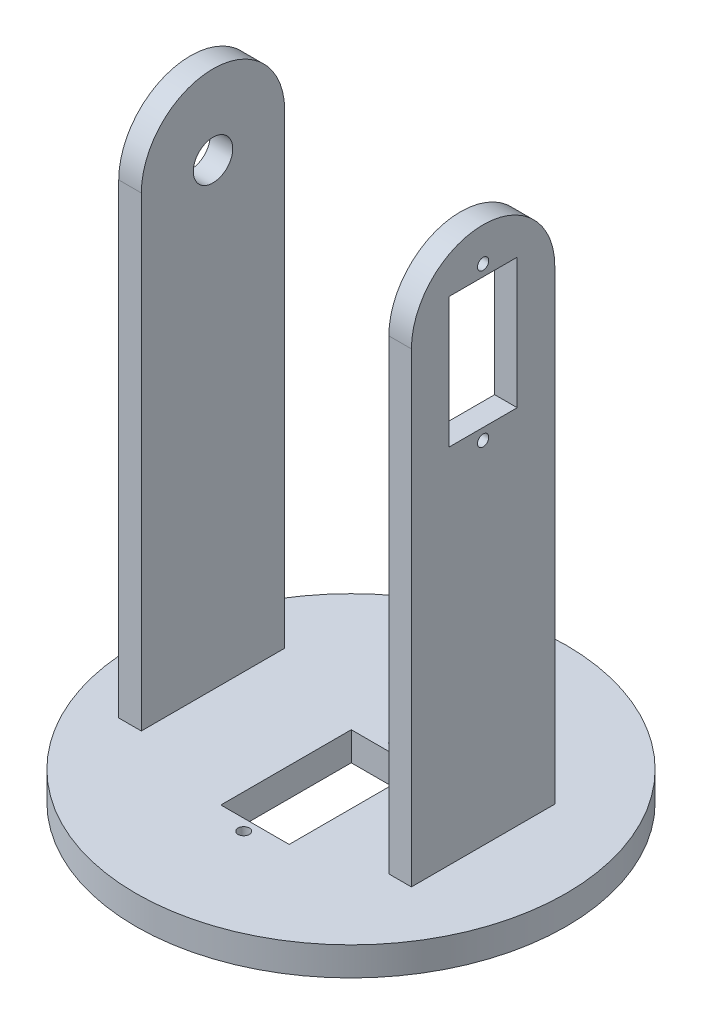
SolidWorks part; units mm, degrees
ref_plane "Front Plane" through (0, 0, 0) normal (0, 0, 1) x (1, 0, 0)
ref_plane "Top Plane" through (0, 0, 0) normal (0, 1, 0) x (1, 0, 0)
ref_plane "Right Plane" through (0, 0, 0) normal (1, 0, 0) x (0, 0, -1)
sketch "Sketch1" plane through (0, 0, 0) normal (0, 1, 0) x (1, 0, 0)
  circle A0 centre (0, 0) radius 38.1
  dimension "D1" = 76.2
extrude "Boss-Extrude1" add sketch "Sketch1" along normal blind 5.08
sketch "Sketch2" plane through (0, 5.08, 0) normal (0, 1, 0) x (1, 0, 0)
  line L1 (-28.448, 12.7) -> (-24.448, 12.7)
  line L2 (-28.448, 12.7) -> (-28.448, -12.7)
  line L3 (-28.448, -12.7) -> (-24.448, -12.7)
  line L4 (-24.448, 12.7) -> (-24.448, -12.7)
  line L5 (19.4, 12.7) -> (23.4, 12.7)
  line L6 (19.4, 12.7) -> (19.4, -12.7)
  line L7 (19.4, -12.7) -> (23.4, -12.7)
  line L8 (23.4, 12.7) -> (23.4, -12.7)
  point P8 (-24.448, 0)
  point P9 (19.4, 0)
  dimension "D1" = 25.4
  dimension "D2" = 25.4
  dimension "D3" = 28.448
  dimension "D4" = 4
  dimension "D5" = 4
  dimension "D6" = 23.4
extrude "Boss-Extrude2" add sketch "Sketch2" along normal blind 95.25
sketch "Sketch3" plane through (23.4, 0, 0) normal (1, 0, 0) x (0, 0, -1)
  line L0 (-12.7, 100.33) -> (12.7, 100.33) construction
  line L1 (-6.05, 92.33) -> (6.05, 92.33)
  line L2 (-6.05, 92.33) -> (-6.05, 69.23)
  line L3 (-6.05, 69.23) -> (6.05, 69.23)
  line L4 (6.05, 92.33) -> (6.05, 69.23)
  line L5 (-6.05, 92.33) -> (6.05, 69.23) construction
  circle A0 centre (0, 67.23) radius 1
  circle A1 centre (0, 94.33) radius 1
  point P4 (0, 100.33)
  point P9 (0, 92.33)
  point P14 (0, 80.78)
  dimension "D4" = 2
  dimension "D5" = 2
  dimension "D1" = 12.1
  dimension "D2" = 23.1
  dimension "D3" = 8
  dimension "D6" = 2
  dimension "D7" = 2
extrude "Cut-Extrude2" cut sketch "Sketch3" against normal up to next
sketch "Sketch4" plane through (23.4, 0, 0) normal (1, 0, 0) x (0, 0, -1)
  line L0 (-12.7, 100.33) -> (-12.7, 87.63)
  line L1 (-12.7, 100.33) -> (-12.7, 5.08) construction
  line L2 (12.7, 100.33) -> (12.7, 5.08) construction
  line L3 (-12.7, 100.33) -> (12.7, 100.33)
  line L4 (12.7, 100.33) -> (12.7, 87.63)
  arc A0 (-12.7, 87.63) -> (12.7, 87.63) centre (0, 87.63) cw
  line M8 (12.7, 5.08) -> (12.7, 100.33)
  line M9 (12.7, 100.33) -> (-12.7, 100.33)
  line M10 (-12.7, 100.33) -> (-12.7, 5.08)
  dimension "D1" = 12.7
extrude "Cut-Extrude3" cut sketch "Sketch4" against normal through all contours A0 L3 M10 | A0 M9 M8 region at (23.4, 97.4932, 9.8632) region at (23.4, 97.4932, -9.8632)
sketch "Sketch5" plane through (-28.448, 0, 0) normal (-1, 0, 0) x (0, 0, 1)
  circle A0 centre (0, 86.33) radius 3.5
  arc A1 (12.7, 87.63) -> (-12.7, 87.63) centre (0, 87.63) ccw construction
  point P5 (0, 100.33)
  dimension "D2" = 7
  dimension "D1" = 14
extrude "Cut-Extrude4" cut sketch "Sketch5" against normal up to next
sketch "Sketch6" plane through (0, 5.08, 0) normal (0, 1, 0) x (1, 0, 0)
  line L0 (-6.05, 6.096) -> (6.05, 6.096)
  line L1 (-6.05, 6.096) -> (-6.05, -17.004)
  line L2 (-6.05, -17.004) -> (6.05, -17.004)
  line L3 (6.05, 6.096) -> (6.05, -17.004)
  circle A1 centre (0, -19.004) radius 1
  circle A2 centre (0, 8.096) radius 1
  point P5 (0, 6.096)
  dimension "D1" = 12.1
  dimension "D3" = 2
  dimension "D4" = 2
  dimension "D2" = 23.1
  dimension "D5" = 2
  dimension "D6" = 2
  dimension "D7" = 6.096
extrude "Cut-Extrude5" cut sketch "Sketch6" against normal up to next
